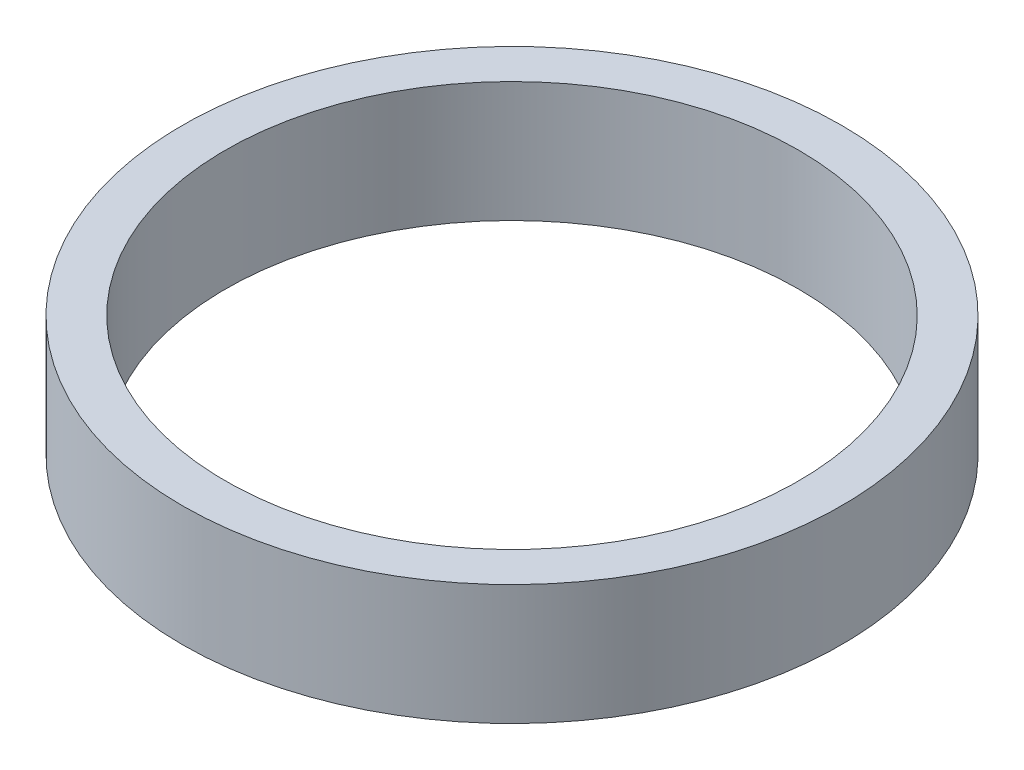
SolidWorks part; units mm, degrees
ref_plane "Front Plane" through (0, 0, 0) normal (0, 0, 1) x (1, 0, 0)
ref_plane "Top Plane" through (0, 0, 0) normal (0, 1, 0) x (1, 0, 0)
ref_plane "Right Plane" through (0, 0, 0) normal (1, 0, 0) x (0, 0, -1)
sketch "Sketch1" plane through (0, 0, 0) normal (0, 1, 0) x (1, 0, 0)
  circle A0 centre (0, 0) radius 57.5
  dimension "FLANGE_OD" = 115
extrude "Boss-Extrude1" add sketch "Sketch1" along normal blind 21
sketch "Sketch2" plane through (0, 0, 0) normal (0, 1, 0) x (1, 0, 0)
  circle A0 centre (0, 0) radius 50
  dimension "BORE_D" = 100
extrude "Cut-Extrude1" cut sketch "Sketch2" along normal through all
sketch "Sketch3" plane through (0, 21, 0) normal (0, 1, 0) x (1, 0, 0)
  circle A0 centre (0, 0) radius 26.5183 construction
  circle A1 centre (-26.5183, 0) radius 1.5
  dimension "BOLT_D" = 3
  dimension "BOLT_PCD" = 53.0365
extrude "Cut-Extrude2" cut sketch "Sketch3" against normal blind 20.6233 rebuild error yes
pattern_circular "CirPattern1" count 8 over 360 rebuild error yes
